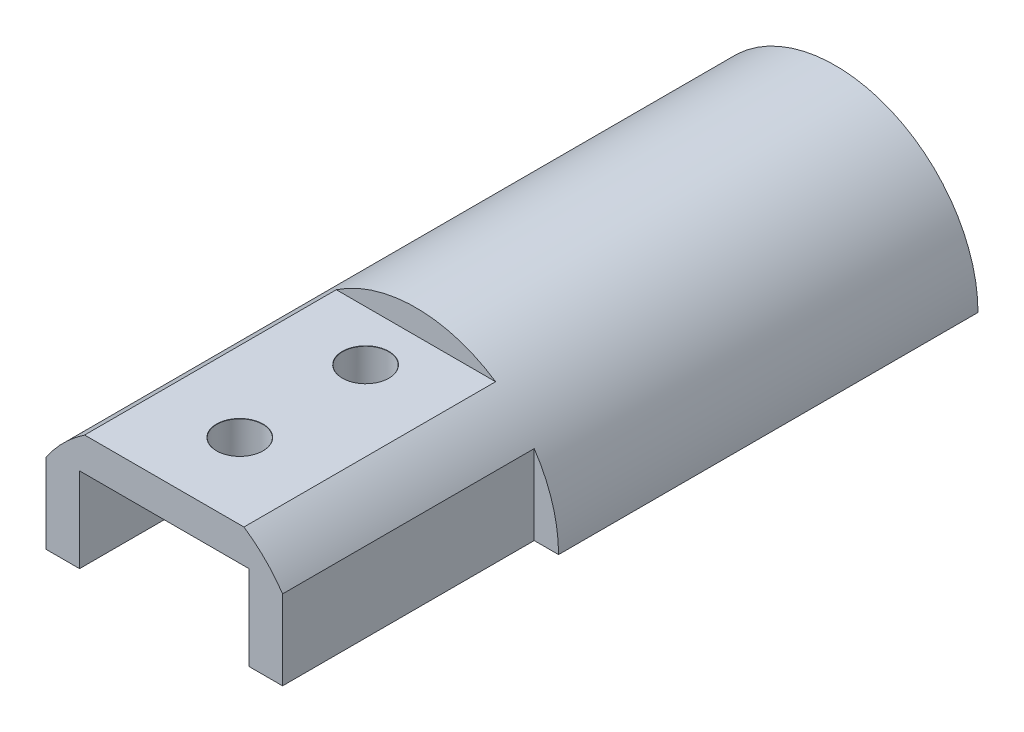
SolidWorks part; units mm, degrees
ref_plane "前视基准面" through (0, 0, 0) normal (0, 0, 1) x (1, 0, 0)
ref_plane "上视基准面" through (0, 0, 0) normal (0, 1, 0) x (1, 0, 0)
ref_plane "右视基准面" through (0, 0, 0) normal (1, 0, 0) x (0, 0, -1)
sketch "草图1" plane through (0, 0, 0) normal (0, 0, 1) x (1, 0, 0)
  circle A0 centre (0, 0) radius 17
  dimension "D1" = 34
extrude "凸台-拉伸1" add sketch "草图1" along normal blind 3
sketch "草图2" plane through (0, 0, 3) normal (0, 0, 1) x (1, 0, 0)
  circle A0 centre (0, 0) radius 17 construction
  circle A1 centre (0, 0) radius 17
  circle A2 centre (0, 0) radius 15
  dimension "D1" = 30
extrude "凸台-拉伸2" add sketch "草图2" along normal blind 40
sketch "草图3" plane through (0, 0, 3) normal (0, 0, 1) x (1, 0, 0)
  circle A0 centre (0, 0) radius 5
  dimension "D1" = 10
extrude "切除-拉伸1" cut sketch "草图3" against normal through all
sketch "草图4" plane through (0, 0, 43) normal (0, 0, 1) x (1, 0, 0)
  line L0 (0, 17) -> (0, -17) construction
  line L1 (-17, 0) -> (0, 0) construction
  line L2 (-4.4431, 10.1) -> (4.4431, 10.1)
  line L7 (10.1, 4.4431) -> (10.1, -4.4431)
  line L8 (-10.1, 4.4431) -> (-10.1, -4.4431)
  line L9 (-4.4431, 10.1) -> (-10.1, 4.4431)
  line L10 (4.4431, 10.1) -> (10.1, 4.4431)
  line L11 (-4.4431, -10.1) -> (-10.1, -4.4431)
  line L12 (-4.4431, -10.1) -> (4.4431, -10.1)
  line L13 (4.4431, -10.1) -> (10.1, -4.4431)
  circle A0 centre (0, 0) radius 17
  point P17 (0, 10.1)
  point P18 (-10.1, 0)
  point P21 (10.1, 0)
  dimension "D1" = 10.1
  dimension "D2" = 10.1
  dimension "D3" = 8
  dimension "D4" = 135
extrude "凸台-拉伸3" add sketch "草图4" along normal blind 7
sketch "草图5" plane through (0, 0, 50) normal (0, 0, 1) x (1, 0, 0)
  line L2 (-9.4968, 14.1) -> (9.4968, 14.1)
  line L4 (-14.1, 9.4968) -> (-14.1, -9.4968)
  line L6 (0, 0) -> (10.1, 10.1) construction
  line L7 (14.1, -9.4968) -> (14.1, 9.4968)
  line L8 (9.4968, -14.1) -> (-9.4968, -14.1)
  line L11 (-10.1, 10.1) -> (-10.1, -10.1)
  line L12 (-10.1, -10.1) -> (10.1, -10.1)
  line L13 (10.1, -10.1) -> (10.1, 10.1)
  line L14 (10.1, 10.1) -> (-10.1, 10.1)
  circle A1 centre (0, 0) radius 17 construction
  arc A2 (-14.1, -9.4968) -> (-9.4968, -14.1) centre (0, 0) ccw
  arc A3 (-9.4968, 14.1) -> (-14.1, 9.4968) centre (0, 0) ccw
  arc A4 (14.1404, 9.4366) -> (9.4366, 14.1404) centre (0, 0) ccw
  arc A5 (14.1, -9.4968) -> (9.4968, -14.1) centre (0, 0) cw
  circle M7 centre (0, 0) radius 17
  dimension "D1" = 4
  dimension "D2" = 4
  dimension "D3" = 20.2
  dimension "D4" = 20.2
extrude "凸台-拉伸4" add sketch "草图5" along normal blind 30 contours L6 A4 L2 L4 M7 | L6 A2 L8 L7 M7 region at (0, 13.7012, 50)
hole_wizard "M5 间隙孔2" positions "草图6" profile "草图7" hole size "M5" standard "ISO" end condition through all
sketch "草图6" plane through (0, 14.1, 0) normal (0, 1, 0) x (1, 0, 0)
  line L2 (-9.4968, -50) -> (9.4968, -50) construction
  line L3 (0, -83) -> (0, -30.4102) construction
  point P0 (0, -56)
  point P2 (0, -71)
  dimension "D1" = 6
  dimension "D2" = 15
sketch "草图7" plane through (0, 14.1, 56) normal (1, 0, 0) x (0, 0, 1)
  line L0 (0, 0) -> (0, 31.1)
  line L1 (0, 31.1) -> (2.75, 31.1)
  line L2 (2.75, 31.1) -> (2.75, 0.025)
  line L3 (2.75, 0.025) -> (2.775, 0)
  line L5 (2.775, 0) -> (0, 0)
  line L6 (-2.75, 0.025) -> (-2.775, 0) construction
  line L11 (0, -6.35) -> (0, 107.95) construction
  dimension "通孔孔直径" = 5.5
  dimension "通孔孔深度" = 31.1
  dimension "近端锥形沉头孔直径" = 5.55
  dimension "近端锥形沉头孔角度" = 90
hole_wizard "M2.5 间隙孔2" positions "草图9" profile "草图10" hole size "M2.5" standard "ISO" end condition through all
sketch "草图9" plane through (0, 0, 3) normal (0, 0, 1) x (1, 0, 0)
  point P0 (11, 0)
  point P11 (11, 0)
  point P12 (11, 0)
  point P13 (11, 0)
  point P20 (11, 0)
  point P21 (11, 0)
  point P22 (11, 0)
  point P31 (7.7782, -7.7782)
  point P32 (0, -11)
  point P33 (-7.7782, -7.7782)
  point P34 (-11, 0)
  point P35 (-7.7782, 7.7782)
  point P36 (0, 11)
  point P37 (7.7782, 7.7782)
  dimension "D1" = 11
  dimension "D2" = 4
  dimension "D3" = 4
  dimension "D4" = 8
sketch "草图10" plane through (11, 0, 3) normal (1, 0, 0) x (0, -1, 0)
  line L0 (0, 0) -> (0, 3)
  line L1 (0, 3) -> (1.45, 3)
  line L2 (1.45, 3) -> (1.45, 0.025)
  line L3 (1.45, 0.025) -> (1.475, 0)
  line L5 (1.475, 0) -> (0, 0)
  line L6 (-1.45, 0.025) -> (-1.475, 0) construction
  line L11 (0, -6.35) -> (0, 107.95) construction
  dimension "通孔孔直径" = 2.9
  dimension "通孔孔深度" = 3
  dimension "近端锥形沉头孔直径" = 2.95
  dimension "近端锥形沉头孔角度" = 90
sketch "草图12" plane through (0, 0, 0) normal (0, 1, 0) x (1, 0, 0)
  line L1 (22.8146, 3.072) -> (-24.3727, 3.072)
  line L2 (22.8146, 3.072) -> (22.8146, -86.2946)
  line L3 (22.8146, -86.2946) -> (-24.3727, -86.2946)
  line L4 (-24.3727, 3.072) -> (-24.3727, -86.2946)
extrude "切除-拉伸2" cut sketch "草图12" against normal blind 18
